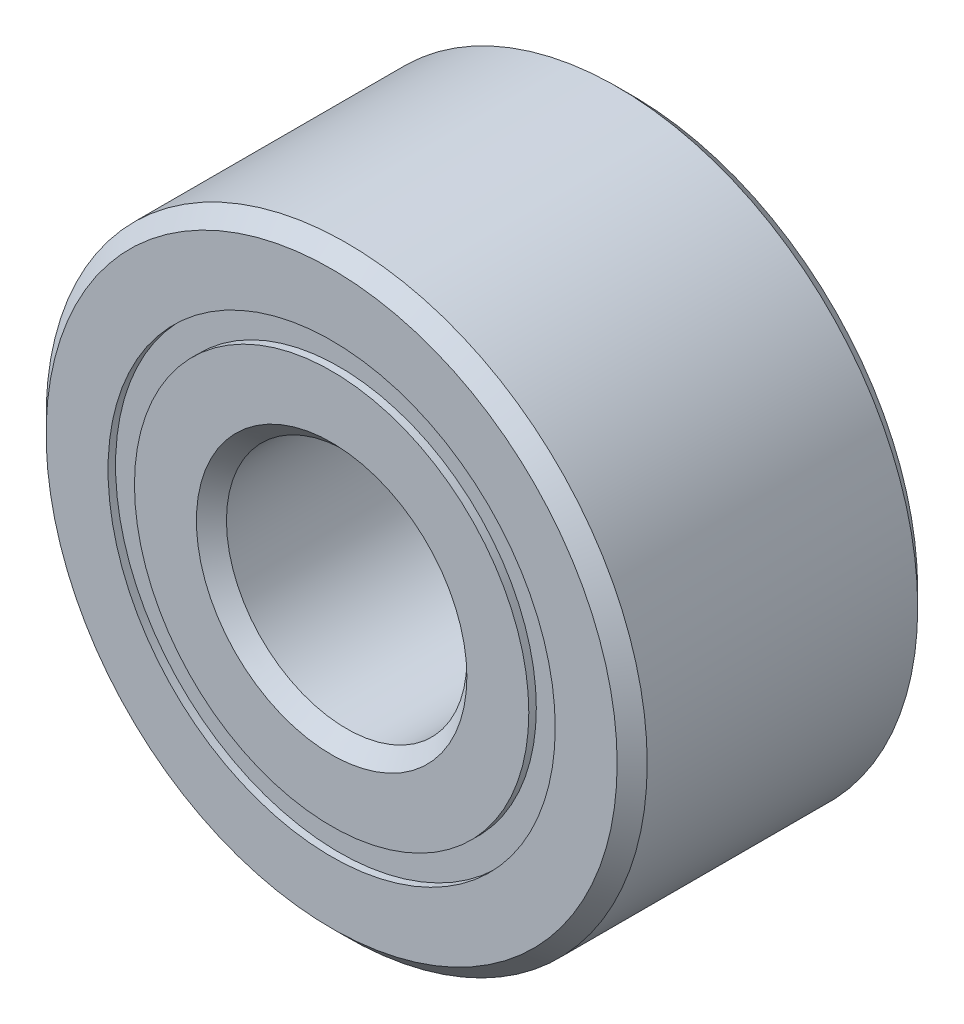
SolidWorks part; units mm, degrees
ref_plane "Front Plane" through (0, 0, 0) normal (0, 0, 1) x (1, 0, 0)
ref_plane "Top Plane" through (0, 0, 0) normal (0, 1, 0) x (1, 0, 0)
ref_plane "Right Plane" through (0, 0, 0) normal (1, 0, 0) x (0, 0, -1)
sketch "Sketch1" plane through (0, 0, 0) normal (1, 0, 0) x (0, 0, -1)
  line L0 (-1.25, 0) -> (1.25, 0) construction
  line L1 (0, 2.5) -> (0, -2.5) construction
  line L2 (1.125, 2.5) -> (-1.125, 2.5)
  line L3 (-1.125, 2.5) -> (-1.25, 2.375)
  line L4 (-1.25, 2.375) -> (-1.25, 1.8599)
  line L5 (-1.25, 1.8599) -> (-0.5556, 1.8599)
  line L6 (1.25, 1.8599) -> (0.5556, 1.8599)
  line L7 (1.25, 2.375) -> (1.25, 1.8599)
  line L8 (1.125, 2.5) -> (1.25, 2.375)
  line L9 (0, 2.5) -> (0, 1.75) construction
  line L10 (0, 1.75) -> (0, 1) construction
  arc A0 (-0.5556, 1.8599) -> (0.5556, 1.8599) centre (0, 1.75) cw
  point P14 (0, 1)
  dimension "Width" = 2.5
  dimension "OD" = 5
  dimension "D1" = 45
  dimension "D2" = 0.125
  dimension "Shaft Dia" = 2
  dimension "D3" = 1.1111
  dimension "D4" = 0.1099
revolve "Revolve1" add sketch "Sketch1" angle 360 about L0
sketch "Sketch3" plane through (0, 0, 0) normal (1, 0, 0) x (0, 0, -1)
  line L0 (-1.25, 1.6401) -> (-0.5556, 1.6401)
  line L1 (0, 2.5) -> (0, -2.5) construction
  line L2 (-1.25, 2.375) -> (-1.25, 1.8599) construction
  line L3 (-1.25, 1.6401) -> (-1.25, 1.125)
  line L4 (-1.125, 2.5) -> (-1.25, 2.375) construction
  line L5 (-1.25, 1.125) -> (-1.125, 1)
  line L6 (-1.125, 1) -> (1.125, 1)
  line L7 (1.125, 2.5) -> (1.125, -2.5) construction
  line L8 (1.125, 1) -> (1.25, 1.125)
  line L9 (1.25, -2.375) -> (1.25, 2.375) construction
  line L10 (1.25, 1.125) -> (1.25, 1.6401)
  line L11 (1.25, 1.6401) -> (0.5556, 1.6401)
  line L13 (1.125, 2.5) -> (1.25, 2.375) construction
  arc A0 (0.5556, 1.8599) -> (-0.5556, 1.8599) centre (0, 1.75) ccw construction
  arc A1 (0.5556, 1.6401) -> (-0.5556, 1.6401) centre (0, 1.75) cw
revolve "Revolve3" add sketch "Sketch3" angle 360 about L0
sketch "Sketch4" plane through (0, 0, 0) normal (1, 0, 0) x (0, 0, -1)
  line L0 (-0.5663, 1.75) -> (0.5663, 1.75)
  arc A2 (-0.5663, 1.75) -> (0.5663, 1.75) centre (0, 1.75) cw
  arc A3 (0.5556, 1.8599) -> (-0.5556, 1.8599) centre (0, 1.75) ccw construction
revolve "Revolve4" add sketch "Sketch4" angle 360 about L0
ref_axis "Axis1" through (0, 0, -1.25) along (0, 0, 1)
pattern_circular "CirPattern1" count 12 every 30 about axis through (0, 0, -1.25) along (0, 0, 1) of bodies 104
sketch "Sketch5" plane through (0, 0, 0) normal (1, 0, 0) x (0, 0, -1)
  line L0 (-1.25, 1.8599) -> (-0.5556, 1.8599) construction
  line L1 (-1.1875, 1.8599) -> (-0.5663, 1.8599)
  line L2 (-1.1875, 1.8599) -> (-1.1875, 1.6401)
  line L3 (-1.1875, 1.6401) -> (-0.5663, 1.6401)
  line L4 (-0.5663, 1.8599) -> (-0.5663, 1.6401)
  line L5 (-1.25, 1.6401) -> (-0.5556, 1.6401) construction
  line L6 (1.25, 1.8599) -> (0.5556, 1.8599) construction
  line L7 (1.1875, 1.8599) -> (0.5663, 1.8599)
  line L8 (1.1875, 1.8599) -> (1.1875, 1.6401)
  line L9 (1.1875, 1.6401) -> (0.5663, 1.6401)
  line L10 (0.5663, 1.8599) -> (0.5663, 1.6401)
  line L11 (1.25, 1.6401) -> (0.5556, 1.6401) construction
  line L12 (-1.125, 2.5) -> (-1.25, 2.375) construction
  point P18 (-1.1875, 2.4375)
revolve "Revolve5" add sketch "Sketch5" angle 360 about L0
sketch "Sketch6" plane through (0, 0, 0) normal (1, 0, 0) x (0, 0, -1)
  line L0 (1.25, 0) -> (-1.25, 0) construction
  line L1 (1.25, 1.8599) -> (0.15, 1.8599)
  line L2 (1.25, 1.8599) -> (1.25, 9.5)
  line L3 (1.25, 9.5) -> (0.15, 9.5)
  line L4 (0.15, 1.8599) -> (0.15, 9.5)
  dimension "Th" = 1.1
  dimension "Flange OD" = 19
revolve "Revolve6" [suppressed] add sketch "Sketch6" angle 360 about L0
equation "\"D2@Sketch1\" = \"Width@Sketch1\"*.05"
equation "\"D3@Sketch1\" = \"Width@Sketch1\"/2.25"
equation "\"D4@Sketch1\" = (((\"OD@Sketch1\"-\"Width@Sketch1\")/2)/3.25)/3.5"
equation "\"D2@CirPattern1\" = 360/\"Balls@CirPattern1\""
